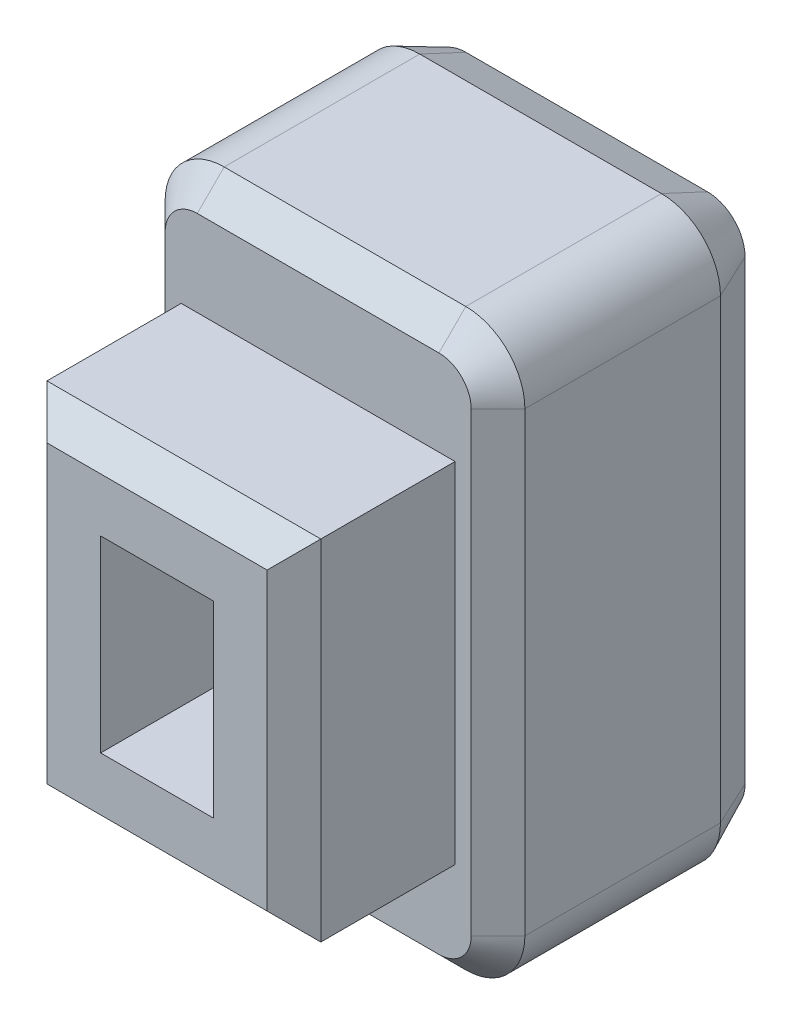
SolidWorks part; units mm, degrees
ref_plane "Plan de face" through (0, 0, 0) normal (0, 0, 1) x (1, 0, 0)
ref_plane "Plan de dessus" through (0, 0, 0) normal (0, 1, 0) x (1, 0, 0)
ref_plane "Plan de droite" through (0, 0, 0) normal (1, 0, 0) x (0, 0, -1)
sketch "Esquisse2" plane through (0, 0, 0) normal (0, 0, 1) x (1, 0, 0)
  line L1 (1.1, 0) -> (5.6, 0)
  line L2 (0, 1.1) -> (0, 9.6)
  line L3 (1.1, 10.7) -> (5.6, 10.7)
  line L4 (6.7, 1.1) -> (6.7, 9.6)
  arc A0 (5.6, 10.7) -> (6.7, 9.6) centre (5.6, 9.6) cw
  arc A1 (5.6, 0) -> (6.7, 1.1) centre (5.6, 1.1) ccw
  arc A2 (1.1, 0) -> (0, 1.1) centre (1.1, 1.1) cw
  arc A3 (0, 9.6) -> (1.1, 10.7) centre (1.1, 9.6) cw
  point P7 (6.7, 10.7)
  point P12 (0, 0)
  point P15 (0, 10.7)
  dimension "D3" = 1.1
  dimension "D1" = 6.7
  dimension "D2" = 10.7
extrude "Boss.-Extru.1" add sketch "Esquisse2" along normal blind 8
sketch "Esquisse3" plane through (0, 0, 8) normal (0, 0, 1) x (1, 0, 0)
  line L1 (2.3, 7.1) -> (4.4, 7.1)
  line L2 (2.3, 3.6) -> (2.3, 7.1)
  line L3 (4.4, 3.6) -> (4.4, 7.1)
  line L4 (6.7, 1.1) -> (6.7, 9.6) construction
  line L6 (5.6, 10.7) -> (1.1, 10.7) construction
  line L7 (0, 9.6) -> (0, 1.1) construction
  line L8 (1.1, 0) -> (5.6, 0) construction
  line L11 (2.3, 3.6) -> (4.4, 3.6)
  line L13 (-7.1761, 5.2) -> (15.2275, 5.2) construction
  dimension "D2" = 2.1
  dimension "D3" = 3.5
  dimension "D4" = 2.3
  dimension "D5" = 3.6
  dimension "D6" = 2.3
  dimension "D9" = 3.6
  dimension "D10" = 5.5
chamfer "Chanfrein1" distance 0.4 angle 65 8 edges at (3.35, 0, 0) (6.3778, 0.3222, 0) (0.3222, 0.3222, 0) (6.7, 5.35, 0) (0, 5.35, 0) (6.3778, 10.3778, 0) (0.3222, 10.3778, 0) (3.35, 10.7, 0) first distance on face at (3.35, 5.35, 0)
extrude "Enlèv. mat.-Extru.4" cut sketch "Esquisse3" against normal blind 3
sketch "Esquisse4" plane through (0, 0, 8) normal (0, 0, 1) x (1, 0, 0)
  line L0 (4.4, 3.6) -> (4.4, 7.1) construction
  line L1 (5.9, 2.1) -> (0.8, 2.1)
  line L2 (5.9, 2.1) -> (5.9, 8.6)
  line L3 (5.9, 8.6) -> (0.8, 8.6)
  line L4 (0.8, 2.1) -> (0.8, 8.6)
  line L5 (2.3, 3.6) -> (4.4, 3.6) construction
  line L6 (2.3, 7.1) -> (2.3, 3.6) construction
  line L7 (4.4, 7.1) -> (2.3, 7.1) construction
  dimension "D1" = 1.5
  dimension "D2" = 1.5
  dimension "D3" = 1.5
  dimension "D4" = 1.5
extrude "Enlèv. mat.-Extru.5" cut sketch "Esquisse4" against normal blind 3 flip side to cut
chamfer "Chanfrein2" distance 0.5 angle 45 12 edges at (6.7, 5.35, 5) (6.3778, 10.3778, 5) (6.3778, 0.3222, 5) (3.35, 10.7, 5) (3.35, 0, 5) (0.3222, 10.3778, 5) (0.3222, 0.3222, 5) (0, 5.35, 5) (5.9, 5.35, 8) (3.35, 8.6, 8) (0.8, 5.35, 8) (3.35, 2.1, 8)
sketch "Esquisse5" plane through (0, 0, 0) normal (0, 0, -1) x (-1, 0, 0)
  line L0 (-0.4, 4.5075) -> (-6.3, 4.5075) construction
  line L1 (-0.4, 1.1) -> (-0.4, 9.6) construction
  line L2 (-6.3, 9.6) -> (-6.3, 1.1) construction
  line L3 (-3.375, -0.9158) -> (-3.375, 11.6549) construction
  line L4 (-3.375, 5.1122) -> (-2.775, 6.1122)
  line L5 (-2.775, 6.1122) -> (-3.175, 6.1122)
  line L6 (-3.175, 6.1122) -> (-3.175, 8.8488)
  line L7 (-3.175, 8.8488) -> (-2.775, 8.8488)
  line L8 (-2.775, 8.8488) -> (-3.375, 9.8488)
  line L9 (-3.375, 9.8488) -> (-3.975, 8.8488)
  line L10 (-3.975, 8.8488) -> (-3.575, 8.8488)
  line L11 (-3.575, 8.8488) -> (-3.575, 6.1122)
  line L12 (-3.575, 6.1122) -> (-4.005, 6.1122)
  line L13 (-4.005, 6.1122) -> (-3.375, 5.1122)
  text T0 "<b>C</b>" font "Century Gothic" height 3.5
  dimension "D1" = 0.4
  dimension "D2" = 0.2
  dimension "D3" = 1
  dimension "D4" = 1
  dimension "D5" = 1
  dimension "D6" = 1
  dimension "D7" = 0.4
  dimension "D8" = 0.4
  dimension "D9" = 0.4
  dimension "D10" = 0.43
extrude "Boss.-Extru.2" add sketch "Esquisse5" along normal blind 0.2
extrude "Enlèv. mat.-Extru.6" cut sketch "Esquisse5<2>" against normal blind 0.2
sketch "Esquisse5<2>" plane through (0, 0, 0) normal (0, 0, -1) x (-1, 0, 0) same geometry as "Esquisse5"
